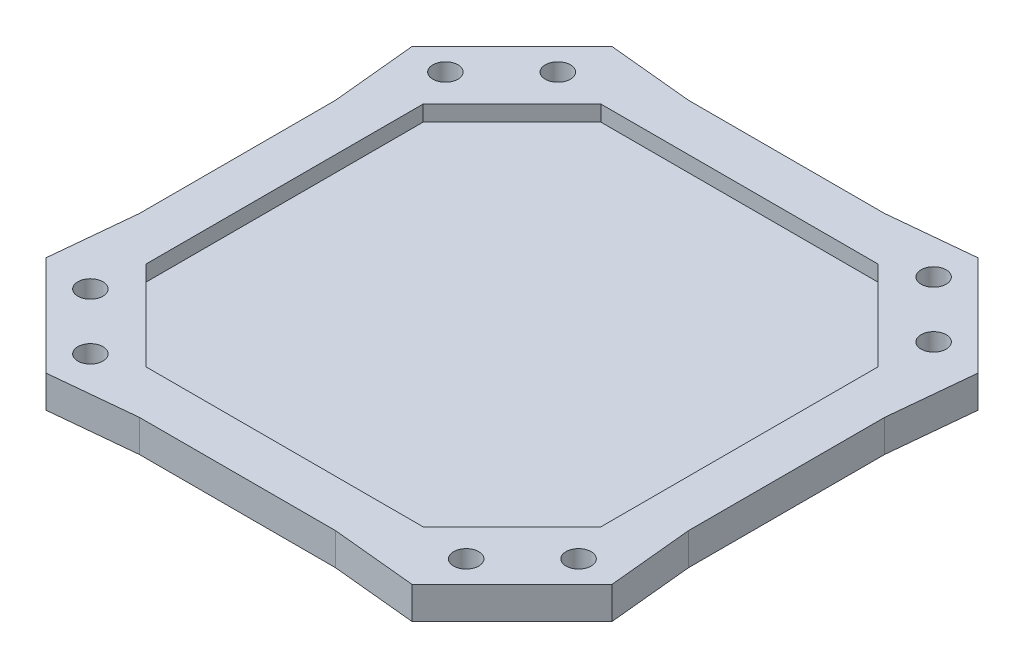
SolidWorks part; units mm, degrees
ref_plane "Front Plane" through (0, 0, 0) normal (0, 0, 1) x (1, 0, 0)
ref_plane "Top Plane" through (0, 0, 0) normal (0, 1, 0) x (1, 0, 0)
ref_plane "Right Plane" through (0, 0, 0) normal (1, 0, 0) x (0, 0, -1)
sketch "Sketch1" plane through (0, 0, 0) normal (0, 1, 0) x (1, 0, 0)
  line L0 (0, 0) -> (84.8528, 84.8528) construction
  line L1 (35, -35) -> (-35, -35) construction
  line L2 (35, -35) -> (35, 35) construction
  line L3 (35, 35) -> (-35, 35) construction
  line L4 (-35, -35) -> (-35, 35) construction
  line L5 (35, -35) -> (-35, 35) construction
  line L6 (35, 35) -> (-35, -35) construction
  line L7 (0, 35) -> (0, -35) construction
  line L8 (-12.5, 35) -> (12.5, 35)
  line L9 (35, 12.5) -> (35, -12.5)
  line L10 (12.5, -35) -> (-12.5, -35)
  line L11 (-35, -12.5) -> (-35, 12.5)
  line L12 (20.5061, 33.234) -> (33.234, 20.5061) construction
  line L13 (23.3345, 36.0624) -> (36.0624, 23.3345)
  line L14 (12.5, 35) -> (23.3345, 36.0624)
  line L15 (36.0624, 23.3345) -> (35, 12.5)
  line L16 (36.0624, -23.3345) -> (23.3345, -36.0624)
  line L17 (35, -12.5) -> (36.0624, -23.3345)
  line L18 (23.3345, -36.0624) -> (12.5, -35)
  line L19 (-23.3345, -36.0624) -> (-36.0624, -23.3345)
  line L20 (-12.5, -35) -> (-23.3345, -36.0624)
  line L21 (-36.0624, -23.3345) -> (-35, -12.5)
  line L22 (-36.0624, 23.3345) -> (-23.3345, 36.0624)
  line L23 (-35, 12.5) -> (-36.0624, 23.3345)
  line L24 (-23.3345, 36.0624) -> (-12.5, 35)
  circle A0 centre (22.6274, 31.1127) radius 1.6
  circle A1 centre (29.7906, 23.9496) radius 1.6
  circle A2 centre (31.1127, -22.6274) radius 1.6
  circle A3 centre (23.9496, -29.7906) radius 1.6
  circle A4 centre (-22.6274, -31.1127) radius 1.6
  circle A5 centre (-29.7906, -23.9496) radius 1.6
  circle A6 centre (-31.1127, 22.6274) radius 1.6
  circle A7 centre (-23.9496, 29.7906) radius 1.6
  point P0 (0, 0)
  dimension "D7" = 3.2
  dimension "D8" = 6
  dimension "D1" = 70
  dimension "D2" = 70
  dimension "D3" = 120
  dimension "D4" = 25
  dimension "D5" = 12.5
  dimension "D9" = 82
  dimension "D10" = 4
  dimension "D11" = 18
  dimension "D12" = 4.1302
  dimension "D6" = 4
  dimension "D13" = 4
extrude "Boss-Extrude2" add sketch "Sketch1" along normal blind 4.1
sketch "Sketch2" plane through (0, 4.1, 0) normal (0, 1, 0) x (1, 0, 0)
  line L0 (0, 35) -> (0, 0) construction
  line L1 (0, 0) -> (-35, 0) construction
  line L2 (-35, -12.5) -> (-35, 12.5) construction
  line L3 (-17.669, 29) -> (17.669, 29)
  line L4 (17.669, 29) -> (29, 17.669)
  line L5 (29, 17.669) -> (29, -17.669)
  line L6 (29, -17.669) -> (17.669, -29)
  line L7 (17.669, -29) -> (-17.669, -29)
  line L8 (-17.669, -29) -> (-29, -17.669)
  line L9 (-29, -17.669) -> (-29, 17.669)
  line L10 (-29, 17.669) -> (-17.669, 29)
  line L12 (-23.3345, -36.0624) -> (-36.0624, -23.3345) construction
  line L13 (23.3345, 36.0624) -> (36.0624, 23.3345) construction
  line L14 (36.0624, -23.3345) -> (23.3345, -36.0624) construction
  line L16 (-36.0624, 23.3345) -> (-23.3345, 36.0624) construction
  line L17 (12.5, -35) -> (-12.5, -35) construction
  line L18 (-12.5, 35) -> (12.5, 35) construction
  dimension "D1" = 6
  dimension "D2" = 9
extrude "Cut-Extrude1" cut sketch "Sketch2" against normal blind 2
sketch "Sketch4" plane through (0, 2.1, 0) normal (0, 1, 0) x (1, 0, 0)
  line L0 (0, 29) -> (0, 0) construction
  line L1 (17.669, 29) -> (-17.669, 29) construction
  line L2 (0, 0) -> (-29, 0) construction
  line L3 (-29, 17.669) -> (-29, -17.669) construction
  line L4 (-24.0792, 13.5676) -> (-16.0792, 6.8995)
  line L5 (-15, 4.5951) -> (-15, -4.5951)
  line L6 (-16.0792, -6.8995) -> (-24.0792, -13.5676)
  line L7 (-29, -11.2631) -> (-29, 11.2631)
  line L8 (-6.8995, 16.0792) -> (-13.5676, 24.0792)
  line L9 (4.5951, 15) -> (-4.5951, 15)
  line L10 (13.5676, 24.0792) -> (6.8995, 16.0792)
  line L11 (-11.2631, 29) -> (11.2631, 29)
  line L12 (16.0792, 6.8995) -> (24.0792, 13.5676)
  line L13 (15, -4.5951) -> (15, 4.5951)
  line L14 (24.0792, -13.5676) -> (16.0792, -6.8995)
  line L15 (29, 11.2631) -> (29, -11.2631)
  line L16 (6.8995, -16.0792) -> (13.5676, -24.0792)
  line L17 (-4.5951, -15) -> (4.5951, -15)
  line L18 (-13.5676, -24.0792) -> (-6.8995, -16.0792)
  line L19 (11.2631, -29) -> (-11.2631, -29)
  arc A0 (-15, -4.5951) -> (-16.0792, -6.8995) centre (-18, -4.5951) cw
  arc A1 (-16.0792, 6.8995) -> (-15, 4.5951) centre (-18, 4.5951) cw
  arc A2 (-24.0792, -13.5676) -> (-29, -11.2631) centre (-26, -11.2631) cw
  arc A3 (-24.0792, 13.5676) -> (-29, 11.2631) centre (-26, 11.2631) ccw
  arc A4 (-4.5951, 15) -> (-6.8995, 16.0792) centre (-4.5951, 18) cw
  arc A5 (6.8995, 16.0792) -> (4.5951, 15) centre (4.5951, 18) cw
  arc A6 (13.5676, 24.0792) -> (11.2631, 29) centre (11.2631, 26) ccw
  arc A7 (-13.5676, 24.0792) -> (-11.2631, 29) centre (-11.2631, 26) cw
  arc A8 (15, 4.5951) -> (16.0792, 6.8995) centre (18, 4.5951) cw
  arc A9 (16.0792, -6.8995) -> (15, -4.5951) centre (18, -4.5951) cw
  arc A10 (24.0792, -13.5676) -> (29, -11.2631) centre (26, -11.2631) ccw
  arc A11 (24.0792, 13.5676) -> (29, 11.2631) centre (26, 11.2631) cw
  arc A12 (4.5951, -15) -> (6.8995, -16.0792) centre (4.5951, -18) cw
  arc A13 (-6.8995, -16.0792) -> (-4.5951, -15) centre (-4.5951, -18) cw
  arc A14 (-13.5676, -24.0792) -> (-11.2631, -29) centre (-11.2631, -26) ccw
  arc A15 (13.5676, -24.0792) -> (11.2631, -29) centre (11.2631, -26) cw
  point P16 (-15, -6)
  point P19 (-15, 6)
  point P22 (-29, -17.669)
  point P25 (-29, 17.669)
  dimension "D4" = 3
  dimension "D1" = 12
  dimension "D2" = 15
  dimension "D3" = 6
  dimension "D5" = 4
extrude "Cut-Extrude2" [suppressed] cut sketch "Sketch4" against normal blind 1.5
sketch "Sketch6" plane through (0, 2.1, 0) normal (0, 1, 0) x (1, 0, 0)
  line L0 (0, 0) -> (84.8528, 84.8528) construction
  line L1 (0, 0) -> (15.25, 0) construction
  line L2 (0, 0) -> (0, 15.25) construction
  line L3 (0, 15.25) -> (15.25, 15.25) construction
  line L4 (15.25, 0) -> (15.25, 15.25) construction
  circle A0 centre (15.25, 15.25) radius 1.5
  dimension "D2" = 3
  dimension "D1" = 15.25
extrude "Cut-Extrude3" [suppressed] cut sketch "Sketch6" against normal through all contours A0
sketch "Sketch7" [suppressed] plane through (0, 2, 0) normal (0, 1, 0) x (1, 0, 0)
  circle A0 centre (15.25, 15.25) radius 4
  circle A1 centre (15.25, 15.25) radius 1.5 construction
  circle A2 centre (15.25, 15.25) radius 1.5
  dimension "D1" = 8
extrude "Boss-Extrude3" [suppressed] add sketch "Sketch7" along normal blind 1.5
ref_axis "Axis1" [suppressed] through (0, 4.2, 0) along (0, -1, 0)
pattern_circular "CirPattern1" [suppressed] count 4 over 360 about axis through (0, 4.2, 0) along (0, -1, 0) of bodies 106
fillet "Fillet1" [suppressed] radius 2
fillet "Fillet2" [suppressed] radius 30
